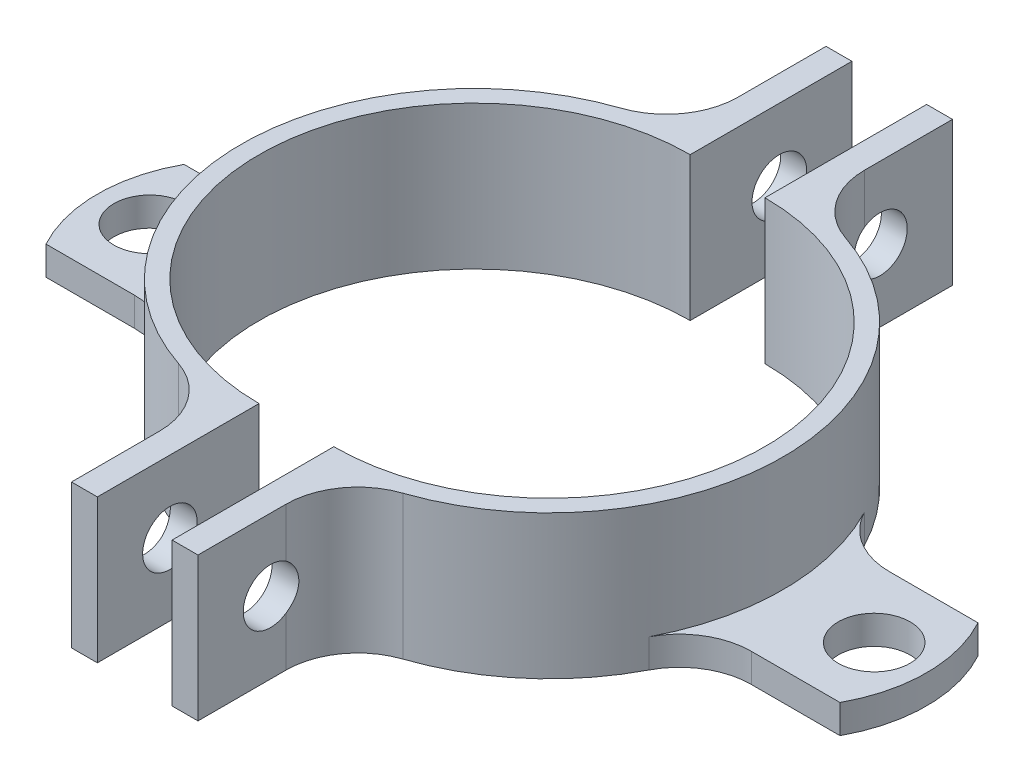
SolidWorks part; units mm, degrees
material "6061 Alloy"
ref_plane "Front Plane" through (0, 0, 0) normal (0, 0, 1) x (1, 0, 0)
ref_plane "Top Plane" through (0, 0, 0) normal (0, 1, 0) x (1, 0, 0)
ref_plane "Right Plane" through (0, 0, 0) normal (1, 0, 0) x (0, 0, -1)
sketch "Sketch1" plane through (0, 0, 0) normal (0, 1, 0) x (1, 0, 0)
  line L0 (0, 0) -> (0, 20.6375)
  line L1 (0, 0) -> (0, -20.6375)
  line L2 (0, 20.6375) -> (0, 33.3375)
  line L3 (0, 33.3375) -> (2.286, 33.3375)
  line L4 (2.286, 33.3375) -> (2.286, 20.5105)
  line L5 (0, -20.6375) -> (0, -33.3375)
  line L6 (0, -33.3375) -> (2.286, -33.3375)
  line L7 (2.286, -33.3375) -> (2.286, -20.5105)
  line L8 (31.7775, 6.0984) -> (19.7159, 6.0984)
  line L9 (19.7159, -6.0984) -> (31.7775, -6.0984)
  arc A0 (0, -19.05) -> (0, 19.05) centre (0, 0) ccw
  arc A1 (0, -20.6375) -> (0, 20.6375) centre (0, 0) ccw
  arc A2 (31.7775, -6.0984) -> (31.7775, 6.0984) centre (20.6375, 0) ccw
  circle A3 centre (28.702, 0) radius 3.175
  dimension "D1" = 38.1
  dimension "D2" = 1.5875
  dimension "D3" = 25.4
  dimension "D8" = 6.35
  dimension "D4" = 12.7
  dimension "D5" = 12.7
  dimension "D6" = 2.286
  dimension "D7" = 2.286
  dimension "D9" = 28.702
extrude "Boss-Extrude1" add sketch "Sketch1" along normal blind 12.7 contours A1 L4 L3 L2 | L1 A1 L0 A0 | A1 L5 L6 L7 region at (0.4615, 0, -19.8438) region at (1.1449, 0, -26.9663) region at (1.1449, 0, 26.9663)
extrude "Boss-Extrude2" add sketch "Sketch1<4>" along normal blind 2.54 contours L9 A2 L8 A1 A3 region at (25.7467, 0, -5.9156)
sketch "Sketch1<4>" plane through (0, 0, 0) normal (0, 1, 0) x (1, 0, 0) same geometry as "Sketch1"
sketch "Sketch4" plane through (2.286, 0, 0) normal (1, 0, 0) x (0, 0, -1)
  circle A0 centre (26.924, 6.35) radius 2.413
  circle A1 centre (-26.924, 6.35) radius 2.413
  dimension "D1" = 4.826
extrude "Cut-Extrude1" cut sketch "Sketch4" against normal up to surface (2.286 mm away) contours A0 up to face at (0, 6.35, -26.1938)
extrude "Cut-Extrude2" cut sketch "Sketch4<3>" against normal blind 2.54
sketch "Sketch4<3>" plane through (2.286, 0, 0) normal (1, 0, 0) x (0, 0, -1) same geometry as "Sketch4"
ref_plane "Plane1" through (-3.302, 0, 0) normal (1, 0, 0) x (0, 0, -1)
fillet "Fillet1" radius 6.35 4 edges at (2.286, 6.35, 20.5105) (19.7159, 1.27, 6.0984) (19.7159, 1.27, -6.0984) (2.286, 6.35, -20.5105)
mirror "Mirror4" about plane through (-3.302, 0, 0) normal (1, 0, 0) of bodies 104
